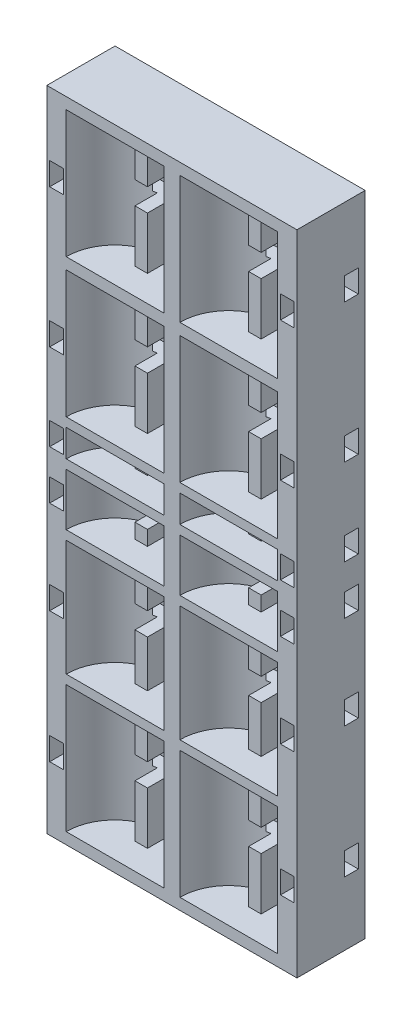
SolidWorks part; units mm, degrees
material "ABS"
ref_plane "Front Plane" through (0, 0, 0) normal (0, 0, 1) x (1, 0, 0)
ref_plane "Top Plane" through (0, 0, 0) normal (0, 1, 0) x (1, 0, 0)
ref_plane "Right Plane" through (0, 0, 0) normal (1, 0, 0) x (0, 0, -1)
sketch "Sketch1" plane through (0, 0, 0) normal (0, 0, 1) x (1, 0, 0)
  line L1 (-49.8113, 37.2642) -> (60.1887, 37.2642)
  line L2 (-49.8113, 37.2642) -> (-49.8113, -247.7358)
  line L3 (-49.8113, -247.7358) -> (60.1887, -247.7358)
  line L4 (60.1887, 37.2642) -> (60.1887, -247.7358)
  dimension "D1" = 110
  dimension "D2" = 285
extrude "Boss-Extrude1" add sketch "Sketch1" along normal blind 30
sketch "Sketch2" plane through (0, 37.2642, 0) normal (0, 1, 0) x (1, 0, 0)
  line L0 (60.1887, -30) -> (-49.8113, -30) construction
  circle A0 centre (-19.8113, -30) radius 21.5
  circle A1 centre (30.1887, -30) radius 21.5
  dimension "D1" = 43
  dimension "D2" = 43
  dimension "D3" = 30
  dimension "D4" = 30
extrude "Cut-Extrude1" cut sketch "Sketch2" against normal through all
sketch "Sketch3" plane through (0, 0, 0) normal (0, 0, -1) x (-1, 0, 0)
  line L0 (-60.1887, -247.7358) -> (-60.1887, 37.2642) construction
  line L1 (49.8113, 37.2642) -> (-60.1887, 37.2642)
  line L2 (49.8113, 37.2642) -> (49.8113, 32.2642)
  line L3 (49.8113, 32.2642) -> (-60.1887, 32.2642)
  line L4 (-60.1887, 37.2642) -> (-60.1887, 32.2642)
  line L5 (49.8113, 37.2642) -> (49.8113, -247.7358) construction
  line L6 (49.8113, -23.7358) -> (-60.1887, -23.7358)
  line L7 (49.8113, -23.7358) -> (49.8113, -28.7358)
  line L8 (49.8113, -28.7358) -> (-60.1887, -28.7358)
  line L9 (-60.1887, -23.7358) -> (-60.1887, -28.7358)
  line L10 (49.8113, 37.2642) -> (49.8113, -247.7358) construction
  line L11 (49.8113, -84.7358) -> (-60.1887, -84.7358)
  line L12 (49.8113, -84.7358) -> (49.8113, -88.7358)
  line L13 (49.8113, -88.7358) -> (-60.1887, -88.7358)
  line L14 (-60.1887, -84.7358) -> (-60.1887, -88.7358)
  line L15 (-60.1887, -247.7358) -> (49.8113, -247.7358)
  line L16 (-60.1887, -247.7358) -> (-60.1887, -242.7358)
  line L17 (-60.1887, -242.7358) -> (49.8113, -242.7358)
  line L18 (49.8113, -247.7358) -> (49.8113, -242.7358)
  line L19 (-60.1887, -247.7358) -> (-60.1887, 37.2642) construction
  line L20 (-60.1887, -186.7358) -> (49.8113, -186.7358)
  line L21 (-60.1887, -186.7358) -> (-60.1887, -182.7358)
  line L22 (-60.1887, -182.7358) -> (49.8113, -182.7358)
  line L23 (49.8113, -186.7358) -> (49.8113, -182.7358)
  line L25 (-60.1887, -127.7358) -> (49.8113, -127.7358)
  line L26 (-60.1887, -127.7358) -> (-60.1887, -131.7358)
  line L27 (-60.1887, -131.7358) -> (49.8113, -131.7358)
  line L28 (49.8113, -127.7358) -> (49.8113, -131.7358)
  line L29 (-60.1887, -104.7358) -> (49.8113, -104.7358)
  line L30 (-60.1887, -104.7358) -> (-60.1887, -100.7358)
  line L31 (-60.1887, -100.7358) -> (49.8113, -100.7358)
  line L32 (49.8113, -104.7358) -> (49.8113, -100.7358)
  dimension "D1" = 5
  dimension "D2" = 5
  dimension "D3" = 56
  dimension "D4" = 4
  dimension "D5" = 56
  dimension "D6" = 5
  dimension "D7" = 4
  dimension "D8" = 56
  dimension "D9" = 51
  dimension "D10" = 4
  dimension "D11" = 4
  dimension "D12" = 23
extrude "Boss-Extrude2" add sketch "Sketch3" against normal up to surface (30 mm away) up to face at (-45.5613, -105.2358, 30)
sketch "Sketch4" plane through (0, 37.2642, 0) normal (0, 1, 0) x (1, 0, 0)
  line L1 (32.9387, -8.5) -> (27.4387, -8.5)
  line L2 (32.9387, -8.5) -> (32.9387, -18.5)
  line L3 (32.9387, -18.5) -> (27.4387, -18.5)
  line L4 (27.4387, -8.5) -> (27.4387, -18.5)
  line L5 (-17.0613, -8.5) -> (-22.5613, -8.5)
  line L6 (-17.0613, -8.5) -> (-17.0613, -18.5)
  line L7 (-17.0613, -18.5) -> (-22.5613, -18.5)
  line L8 (-22.5613, -8.5) -> (-22.5613, -18.5)
  arc A0 (51.6887, -30) -> (8.6887, -30) centre (30.1887, -30) ccw construction
  arc A1 (1.6887, -30) -> (-41.3113, -30) centre (-19.8113, -30) ccw construction
  point P8 (30.1887, -8.5)
  point P9 (-19.8113, -8.5)
  point P13 (-19.8113, -8.5)
  point P17 (30.1887, -8.5)
  dimension "D1" = 10
  dimension "D2" = 10
  dimension "D3" = 5.5
  dimension "D4" = 5.5
extrude "Boss-Extrude4" add sketch "Sketch4" against normal through all
sketch "Sketch5" plane through (0, 0, 30) normal (0, 0, 1) x (1, 0, 0)
  line L0 (-48.5613, -247.7358) -> (-48.5613, 37.2642) construction
  line L1 (-49.8113, -247.7358) -> (60.1887, -247.7358) construction
  line L2 (60.1887, 37.2642) -> (-49.8113, 37.2642) construction
  line L3 (-42.5613, 37.2642) -> (-42.5613, -247.7358) construction
  line L4 (-49.8113, 37.2642) -> (-49.8113, -247.7358) construction
  line L5 (-41.3113, -127.7358) -> (1.6887, -127.7358) construction
  line L6 (-48.5613, -219.7358) -> (-42.5613, -219.7358)
  line L7 (-48.5613, -219.7358) -> (-48.5613, -209.7358)
  line L8 (-48.5613, -209.7358) -> (-42.5613, -209.7358)
  line L9 (-42.5613, -219.7358) -> (-42.5613, -209.7358)
  line L10 (-48.5613, -162.2358) -> (-42.5613, -162.2358)
  line L11 (-48.5613, -162.2358) -> (-48.5613, -152.2358)
  line L12 (-48.5613, -152.2358) -> (-42.5613, -152.2358)
  line L13 (-42.5613, -162.2358) -> (-42.5613, -152.2358)
  line L14 (-48.5613, -121.2358) -> (-42.5613, -121.2358)
  line L15 (-48.5613, -121.2358) -> (-48.5613, -111.2358)
  line L16 (-48.5613, -111.2358) -> (-42.5613, -111.2358)
  line L17 (-42.5613, -121.2358) -> (-42.5613, -111.2358)
  line L22 (-48.5613, -99.7358) -> (-42.5613, -99.7358)
  line L23 (-48.5613, -99.7358) -> (-48.5613, -89.7358)
  line L24 (-48.5613, -89.7358) -> (-42.5613, -89.7358)
  line L25 (-42.5613, -99.7358) -> (-42.5613, -89.7358)
  line L26 (-48.5613, -61.7358) -> (-42.5613, -61.7358)
  line L27 (-48.5613, -61.7358) -> (-48.5613, -51.7358)
  line L28 (-48.5613, -51.7358) -> (-42.5613, -51.7358)
  line L29 (-42.5613, -61.7358) -> (-42.5613, -51.7358)
  line L30 (-48.5613, -0.7358) -> (-42.5613, -0.7358)
  line L31 (-48.5613, -0.7358) -> (-48.5613, 9.2642)
  line L32 (-48.5613, 9.2642) -> (-42.5613, 9.2642)
  line L33 (-42.5613, -0.7358) -> (-42.5613, 9.2642)
  line L35 (1.6887, -88.7358) -> (-41.3113, -88.7358) construction
  line L36 (1.6887, -28.7358) -> (-41.3113, -28.7358) construction
  line L37 (1.6887, 32.2642) -> (-41.3113, 32.2642) construction
  point P38 (-48.5613, -214.7358)
  point P39 (-42.5613, -214.7358)
  point P40 (-42.5613, -157.2358)
  point P41 (-42.5613, -116.2358)
  point P47 (-42.5613, -94.7358)
  point P50 (-42.5613, -56.7358)
  point P53 (-42.5613, 4.2642)
  dimension "D1" = 1.25
  dimension "D2" = 6
  dimension "D3" = 10
  dimension "D4" = 10
  dimension "D5" = 10
  dimension "D7" = 10
  dimension "D8" = 10
  dimension "D9" = 10
  dimension "D10" = 33
  dimension "D11" = 57.5
  dimension "D12" = 11.5
  dimension "D14" = 6
  dimension "D15" = 28
  dimension "D16" = 28
extrude "Cut-Extrude2" cut sketch "Sketch5" against normal blind 27
sketch "Sketch6" plane through (-49.8113, 0, 0) normal (-1, 0, 0) x (0, 0, 1)
  line L0 (9, -61.7358) -> (3, -61.7358)
  line L5 (9, -121.2358) -> (3, -121.2358)
  line L10 (9, -121.2358) -> (9, -111.2358)
  line L15 (9, -111.2358) -> (3, -111.2358)
  line L20 (3, -121.2358) -> (3, -111.2358)
  line L25 (9, -61.7358) -> (9, -51.7358)
  line L30 (9, -99.7358) -> (3, -99.7358)
  line L35 (3, -247.7358) -> (3, 37.2642) construction
  line L36 (9, -219.7358) -> (3, -219.7358)
  line L37 (9, -219.7358) -> (9, -209.7358)
  line L38 (9, -209.7358) -> (3, -209.7358)
  line L39 (3, -219.7358) -> (3, -209.7358)
  line L40 (30, -247.7358) -> (0, -247.7358) construction
  line L41 (30, 37.2642) -> (0, 37.2642) construction
  line L42 (0, 37.2642) -> (0, -247.7358) construction
  line L43 (9, -51.7358) -> (3, -51.7358)
  line L44 (9, -0.7358) -> (3, -0.7358)
  line L45 (9, -0.7358) -> (9, 9.2642)
  line L46 (9, 9.2642) -> (3, 9.2642)
  line L47 (3, -0.7358) -> (3, 9.2642)
  line L48 (9, -99.7358) -> (9, -89.7358)
  line L49 (9, -89.7358) -> (3, -89.7358)
  line L50 (3, -99.7358) -> (3, -89.7358)
  line L51 (3, -61.7358) -> (3, -51.7358)
  line L52 (9, -162.2358) -> (3, -162.2358)
  line L53 (9, -162.2358) -> (9, -152.2358)
  line L54 (9, -152.2358) -> (3, -152.2358)
  line L55 (3, -162.2358) -> (3, -152.2358)
  point P28 (3, -214.7358)
  point P34 (3, -157.2358)
  point P35 (3, -116.2358)
  point P36 (9, 4.2642)
  point P37 (3, -56.7358)
  point P38 (3, -94.7358)
  dimension "D1" = 10
  dimension "D2" = 90.5
  dimension "D3" = 3
  dimension "D4" = 10
  dimension "D5" = 131.5
  dimension "D6" = 10
  dimension "D7" = 6
  dimension "D8" = 10
  dimension "D9" = 33
  dimension "D10" = 10
  dimension "D11" = 94
  dimension "D12" = 33
  dimension "D13" = 10
  dimension "D14" = 132
extrude "Cut-Extrude3" cut sketch "Sketch6" against normal through all and the other way through all
sketch "Sketch7" plane through (0, 0, 30) normal (0, 0, 1) x (1, 0, 0)
  line L0 (5.1887, 37.2642) -> (5.1887, -247.7358) construction
  line L1 (60.1887, 37.2642) -> (-49.8113, 37.2642) construction
  line L2 (-49.8113, -247.7358) -> (60.1887, -247.7358) construction
ref_plane "Plane1" through (5.1887, 0, 0) normal (1, 0, 0) x (0, 0, -1)
mirror "Mirror1" about plane through (5.1887, 0, 0) normal (1, 0, 0) of "Cut-Extrude2"
fillet "Fillet1" radius 5 12 edges at (52.9387, 4.2642, 9) (52.9387, -56.7358, 9) (52.9387, -94.7358, 9) (52.9387, -116.2358, 9) (52.9387, -157.2358, 9) (52.9387, -214.7358, 9) (-42.5613, 4.2642, 9) (-42.5613, -56.7358, 9) (-42.5613, -94.7358, 9) (-42.5613, -116.2358, 9) (-42.5613, -157.2358, 9) (-42.5613, -214.7358, 9)
sketch "Sketch8" plane through (0, 0, 3) normal (0, 0, 1) x (1, 0, 0)
  line L1 (-24.4211, 9.2642) -> (-15.2015, 9.2642)
  line L2 (-24.4211, 9.2642) -> (-24.4211, -0.7358)
  line L3 (-24.4211, -0.7358) -> (-15.2015, -0.7358)
  line L4 (-15.2015, 9.2642) -> (-15.2015, -0.7358)
  line L5 (-24.4211, -51.7358) -> (-15.2015, -51.7358)
  line L6 (-24.4211, -51.7358) -> (-24.4211, -61.7358)
  line L7 (-24.4211, -61.7358) -> (-15.2015, -61.7358)
  line L8 (-15.2015, -51.7358) -> (-15.2015, -61.7358)
  line L9 (-24.4211, -89.7358) -> (-15.2015, -89.7358)
  line L10 (-24.4211, -89.7358) -> (-24.4211, -99.7358)
  line L11 (-24.4211, -99.7358) -> (-15.2015, -99.7358)
  line L12 (-15.2015, -89.7358) -> (-15.2015, -99.7358)
  line L13 (-24.4211, -111.2358) -> (-15.2015, -111.2358)
  line L14 (-24.4211, -111.2358) -> (-24.4211, -121.2358)
  line L15 (-24.4211, -121.2358) -> (-15.2015, -121.2358)
  line L16 (-15.2015, -111.2358) -> (-15.2015, -121.2358)
  line L17 (-24.4211, -152.2358) -> (-15.2015, -152.2358)
  line L18 (-24.4211, -152.2358) -> (-24.4211, -162.2358)
  line L19 (-24.4211, -162.2358) -> (-15.2015, -162.2358)
  line L20 (-15.2015, -152.2358) -> (-15.2015, -162.2358)
  line L21 (-24.4211, -209.7358) -> (-15.2015, -209.7358)
  line L22 (-24.4211, -209.7358) -> (-24.4211, -219.7358)
  line L23 (-24.4211, -219.7358) -> (-15.2015, -219.7358)
  line L24 (-15.2015, -209.7358) -> (-15.2015, -219.7358)
extrude "Cut-Extrude4" cut sketch "Sketch8" along normal through all
mirror "Mirror2" about plane through (5.1887, 0, 0) normal (1, 0, 0) of "Cut-Extrude4"
sketch "Sketch9" plane through (0, 0, 0) normal (0, 0, -1) x (-1, 0, 0)
  line L1 (28.1947, -165.8358) -> (31.4279, -165.8358)
  line L2 (31.4279, -165.8358) -> (33.0445, -163.0358)
  line L3 (33.0445, -163.0358) -> (31.4279, -160.2358)
  line L4 (31.4279, -160.2358) -> (28.1947, -160.2358)
  line L5 (28.1947, -160.2358) -> (26.5782, -163.0358)
  line L6 (26.5782, -163.0358) -> (28.1947, -165.8358)
  line L7 (-41.8053, -165.8358) -> (-38.5721, -165.8358)
  line L8 (-38.5721, -165.8358) -> (-36.9555, -163.0358)
  line L9 (-36.9555, -163.0358) -> (-38.5721, -160.2358)
  line L10 (-38.5721, -160.2358) -> (-41.8053, -160.2358)
  line L11 (-41.8053, -160.2358) -> (-43.4218, -163.0358)
  line L12 (-43.4218, -163.0358) -> (-41.8053, -165.8358)
  line L13 (28.1947, -53.0358) -> (31.4279, -53.0358)
  line L14 (31.4279, -53.0358) -> (33.0445, -50.2358)
  line L15 (33.0445, -50.2358) -> (31.4279, -47.4358)
  line L16 (31.4279, -47.4358) -> (28.1947, -47.4358)
  line L17 (28.1947, -47.4358) -> (26.5782, -50.2358)
  line L18 (26.5782, -50.2358) -> (28.1947, -53.0358)
  line L19 (-41.8053, -53.0358) -> (-38.5721, -53.0358)
  line L20 (-38.5721, -53.0358) -> (-36.9555, -50.2358)
  line L21 (-36.9555, -50.2358) -> (-38.5721, -47.4358)
  line L22 (-38.5721, -47.4358) -> (-41.8053, -47.4358)
  line L23 (-41.8053, -47.4358) -> (-43.4218, -50.2358)
  line L24 (-43.4218, -50.2358) -> (-41.8053, -53.0358)
  circle A0 centre (29.8113, -163.0358) radius 2.8 construction
  circle A1 centre (-40.1887, -163.0358) radius 2.8 construction
  circle A2 centre (29.8113, -50.2358) radius 2.8 construction
  circle A3 centre (-40.1887, -50.2358) radius 2.8 construction
extrude "Cut-Extrude5" cut sketch "Sketch9" against normal blind 2.6
